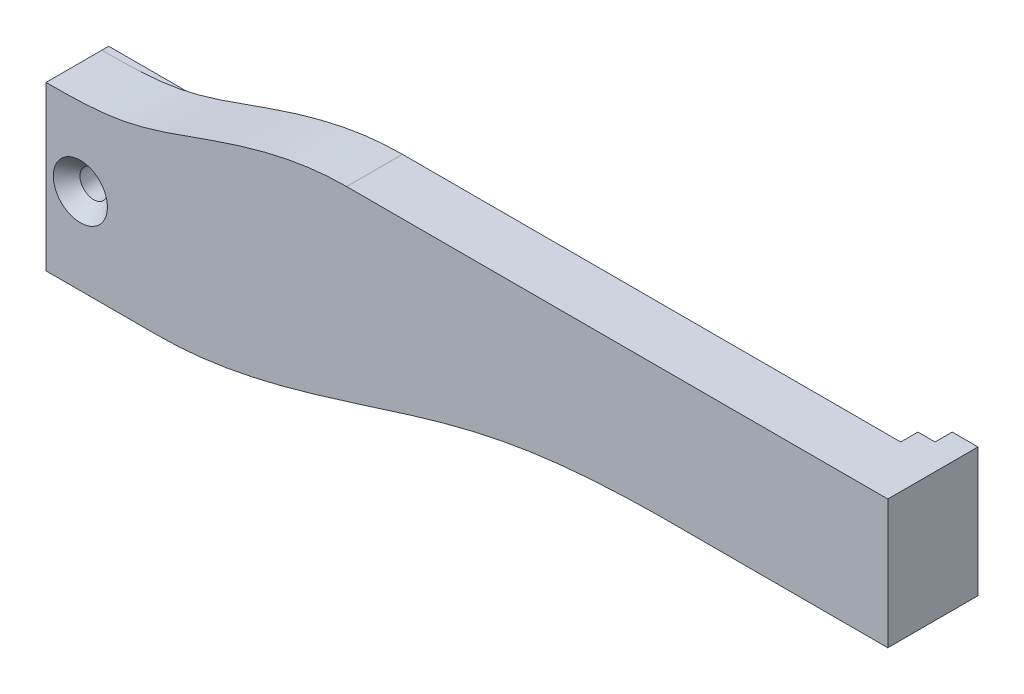
SolidWorks part; units mm, degrees
ref_plane "Front Plane" through (0, 0, 0) normal (0, 0, 1) x (1, 0, 0)
ref_plane "Top Plane" through (0, 0, 0) normal (0, 1, 0) x (1, 0, 0)
ref_plane "Right Plane" through (0, 0, 0) normal (1, 0, 0) x (0, 0, -1)
sketch "Sketch1" plane through (0, 0, 0) normal (0, 0, 1) x (1, 0, 0)
  line L1 (-53.7227, 46.4585) -> (44.2773, 46.4585)
  line L2 (-53.7227, 46.4585) -> (-53.7227, 72.4585)
  line L3 (-53.7227, 72.4585) -> (44.2773, 72.4585)
  line L4 (44.2773, 46.4585) -> (44.2773, 72.4585)
  dimension "D1" = 98
  dimension "D2" = 26
extrude "Boss-Extrude1" add sketch "Sketch1" along normal blind 6.5
sketch "Sketch3" plane through (0, 0, 0) normal (0, 0, -1) x (-1, 0, 0)
  line L0 (-44.2773, 72.4585) -> (-44.2773, 57.4585)
  line L1 (-44.2773, 46.4585) -> (-44.2773, 72.4585) construction
  line L2 (-44.2773, 57.4585) -> (-42.2773, 57.4585)
  line L3 (-42.2773, 57.4585) -> (-42.2773, 70.4585)
  line L4 (-42.2773, 70.4585) -> (-39.2773, 70.4585)
  line L5 (-39.2773, 70.4585) -> (-39.2773, 72.4585)
  line L12 (-39.2773, 72.4585) -> (-44.2773, 72.4585)
  line L21 (53.7227, 46.4585) -> (-44.2773, 46.4585) construction
  dimension "D1" = 26
  dimension "D2" = 2
  dimension "D3" = 2
  dimension "D4" = 5
  dimension "D5" = 11
extrude "Boss-Extrude2" add sketch "Sketch3" along normal blind 2
sketch "Sketch4" plane through (0, 0, 0) normal (0, 0, -1) x (-1, 0, 0)
  line L0 (-44.2773, 57.4585) -> (-19.2773, 57.4585)
  line L1 (-44.2773, 72.4585) -> (-44.2773, 57.4585) construction
  line L2 (53.7227, 46.4585) -> (-44.2773, 46.4585) construction
  line L4 (-44.2773, 57.4585) -> (-42.2773, 57.4585) construction
  line L5 (53.7227, 72.4585) -> (53.7227, 46.4585) construction
  line L6 (-44.2773, 57.4585) -> (-44.2773, 46.4585)
  line L7 (-44.2773, 46.4585) -> (40.7227, 46.4585)
  line L8 (-39.2773, 72.4585) -> (53.7227, 72.4585) construction
  line L9 (18.7227, 72.4585) -> (53.7227, 72.4585)
  line L10 (53.7227, 72.4585) -> (53.7227, 65.4585)
  spline S0 degree 3 poles (-19.2773, 57.4585) (-7.8329, 57.4585) (8.9041, 55.154) (29.5296, 46.4585) (40.7227, 46.4585) knots 0 0 0 0 0.448706 1 1 1 1
  spline S1 degree 3 poles (18.7227, 72.4585) (24.2378, 72.4585) (33.0452, 69.9965) (44.1784, 65.5489) (50.9611, 65.4585) (53.7227, 65.4585) knots 0 0 0 0 0.451492 0.761184 1 1 1 1
  dimension "D2" = 13
  dimension "D4" = 35
  dimension "D1" = 25
  dimension "D3" = 19
extrude "Cut-Extrude2" cut sketch "Sketch4" against normal through all and the other way through all
sketch "Sketch5" plane through (0, 0, 0) normal (0, 0, -1) x (-1, 0, 0)
  line L0 (43.2227, 46.4585) -> (40.7227, 46.4585)
  line L1 (40.7227, 64.9585) -> (41.2227, 65.4585)
  line L2 (53.7227, 46.4585) -> (40.7227, 46.4585) construction
  line L3 (40.7227, 46.4585) -> (40.7227, 64.9585)
  line L4 (41.2227, 65.4585) -> (53.7227, 65.4585)
  line L5 (53.7227, 65.4585) -> (53.7227, 46.4585) construction
  line L6 (53.7227, 65.4585) -> (53.7227, 62.9585)
  line L7 (53.7227, 62.9585) -> (44.1227, 62.9585)
  line L8 (43.2227, 62.0585) -> (43.2227, 46.4585)
  arc A0 (44.1227, 62.9585) -> (43.2227, 62.0585) centre (44.1227, 62.0585) ccw
  point P5 (40.7227, 65.4585)
  dimension "D5" = 0.9
  dimension "D1" = 13
  dimension "D2" = 19
  dimension "D3" = 2.5
  dimension "D4" = 2.5
extrude "Boss-Extrude3" add sketch "Sketch5" along normal blind 0.8
sketch "Sketch6" plane through (0, 0, -2) normal (0, 0, -1) x (-1, 0, 0)
  line L0 (-39.2773, 72.4585) -> (-44.2773, 72.4585) construction
  line L1 (-44.2773, 72.4585) -> (-41.2773, 72.4585)
  line L2 (-44.2773, 72.4585) -> (-44.2773, 57.4585)
  line L3 (-44.2773, 57.4585) -> (-41.2773, 57.4585)
  line L4 (-41.2773, 72.4585) -> (-41.2773, 57.4585)
  line L5 (-19.2773, 57.4585) -> (-42.2773, 57.4585) construction
  line L6 (-44.2773, 57.4585) -> (-44.2773, 72.4585) construction
  dimension "D1" = 3
extrude "Boss-Extrude4" add sketch "Sketch6" along normal blind 2
chamfer "Chamfer1" distance 0.8 angle 45 1 edges at (42.2773, 63.9585, -2)
hole_wizard "CSK for M3 Flat Head Machine Screw1" positions "Sketch10" profile "Sketch11" countersink size "M3" standard "ANSI Metric" end condition through all
sketch "Sketch10" plane through (0, 0, 6.5) normal (0, 0, 1) x (1, 0, 0)
  point P0 (-49.7227, 56.4585)
sketch "Sketch11" plane through (-49.7227, 56.4585, 6.5) normal (1, 0, 0) x (0, -1, 0)
  line L0 (0, 0) -> (0, 10.5)
  line L1 (0, 10.5) -> (1.6, 10.5)
  line L2 (1.6, 10.5) -> (1.6, 1.55)
  line L3 (1.6, 1.55) -> (3.15, 0)
  line L5 (3.15, 0) -> (0, 0)
  line L6 (-1.6, 1.55) -> (-3.15, 0) construction
  line L11 (0, -6.35) -> (0, 107.95) construction
  dimension "Thru Hole Dia." = 3.2
  dimension "Thru Hole Depth" = 10.5
  dimension "Near C'Sink Dia." = 6.3
  dimension "Near C'Sink Angle" = 90
sketch "Sketch12" plane through (0, 0, 0) normal (0, 0, -1) x (-1, 0, 0)
  circle A0 centre (19.6477, 68.8835) radius 2
  dimension "D1" = 4
extrude "Cut-Extrude3" cut sketch "Sketch12" against normal blind 5
